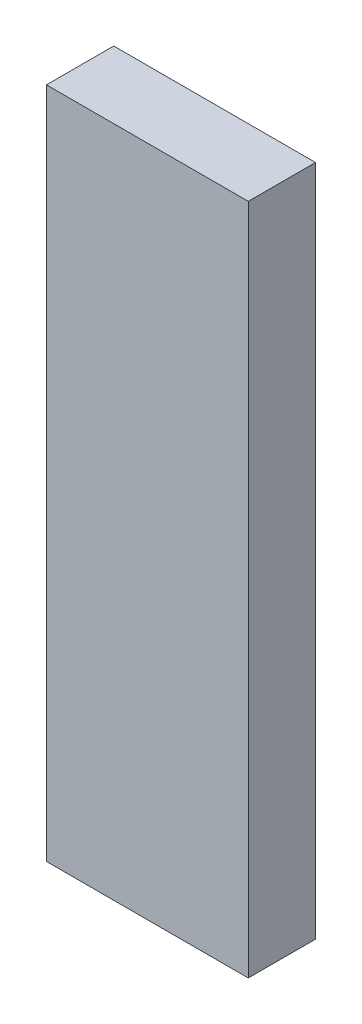
SolidWorks part; units mm, degrees
material "自定义塑料"
ref_plane "前视基准面" through (0, 0, 0) normal (0, 0, 1) x (1, 0, 0)
ref_plane "上视基准面" through (0, 0, 0) normal (0, 1, 0) x (1, 0, 0)
ref_plane "右视基准面" through (0, 0, 0) normal (1, 0, 0) x (0, 0, -1)
sketch "草图1" plane through (0, 0, 0) normal (1, 0, 0) x (0, 0, -1)
  line L1 (-10, -100) -> (10, -100)
  line L2 (-10, -100) -> (-10, 100)
  line L3 (-10, 100) -> (10, 100)
  line L4 (10, -100) -> (10, 100)
  line L5 (-10, -100) -> (10, 100) construction
  line L6 (-10, 100) -> (10, -100) construction
  point P0 (0, 0)
extrude "凸台-拉伸1" add sketch "草图1" along normal blind 30 and the other way blind 30
